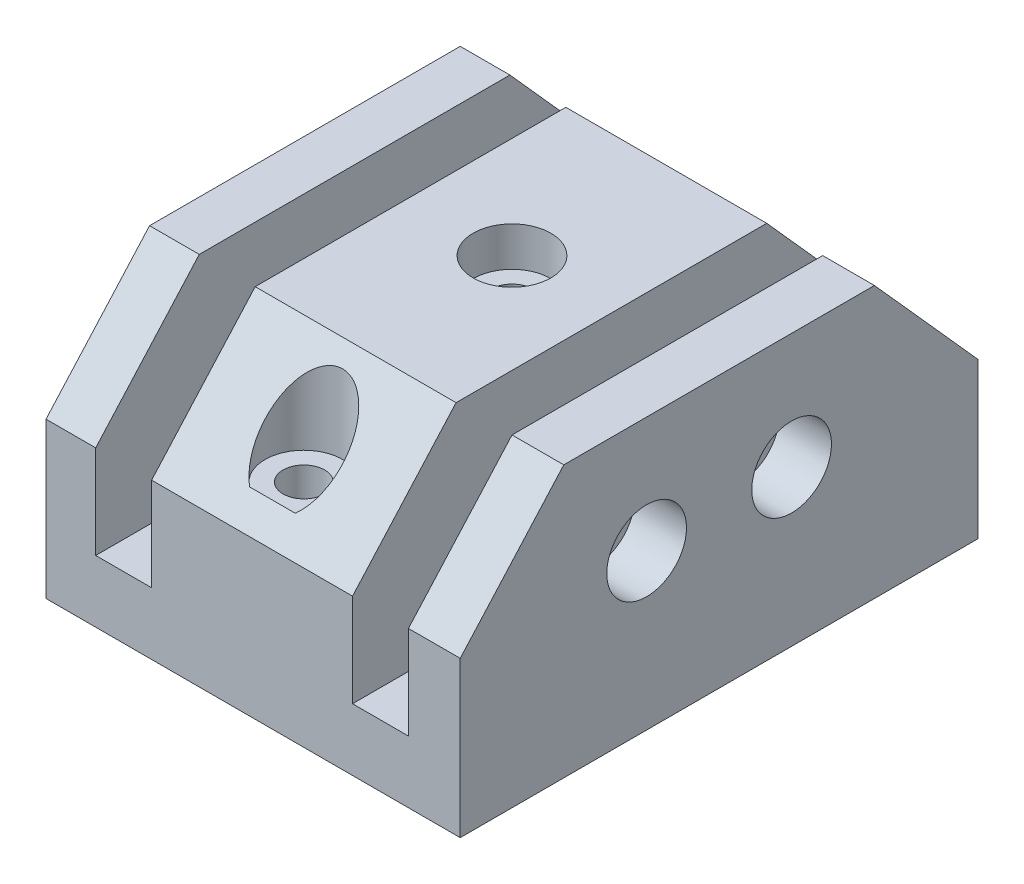
SolidWorks part; units mm, degrees
ref_plane "Front Plane" through (0, 0, 0) normal (0, 0, 1) x (1, 0, 0)
ref_plane "Top Plane" through (0, 0, 0) normal (0, 1, 0) x (1, 0, 0)
ref_plane "Right Plane" through (0, 0, 0) normal (1, 0, 0) x (0, 0, -1)
sketch "Sketch1" plane through (0, 0, 0) normal (1, 0, 0) x (0, 0, -1)
  line L1 (0, 0) -> (63.5, 0)
  line L2 (0, 0) -> (0, 6.35)
  line L3 (0, 6.35) -> (63.5, 6.35)
  line L4 (63.5, 0) -> (63.5, 6.35)
  dimension "D1" = 6.35
  dimension "D2" = 63.5
extrude "Boss-Extrude1" add sketch "Sketch1" against normal blind 50.8
sketch "Sketch2" plane through (0, 0, 0) normal (1, 0, 0) x (0, 0, -1)
  line L0 (0, 6.35) -> (0, 19.05)
  line L1 (0, 19.05) -> (12.7, 33.249)
  line L2 (12.7, 33.249) -> (50.8, 33.249)
  line L3 (50.8, 33.249) -> (63.5, 19.05)
  line L4 (63.5, 19.05) -> (63.5, 6.35)
  line L5 (63.5, 6.35) -> (0, 6.35)
  point P7 (31.75, 33.249)
  point P10 (31.75, 6.35)
  dimension "D1" = 38.1
  dimension "D2" = 12.7
  dimension "D3" = 12.7
  dimension "D4" = 19.05
  dimension "D5" = 19.05
extrude "Boss-Extrude2" add sketch "Sketch2" against normal blind 50.8
sketch "Sketch10" plane through (0, 0, -63.5) normal (0, 0, -1) x (-1, 0, 0)
  line L1 (50.8, 33.249) -> (0, 33.249) construction
  line L3 (6.35, 7.62) -> (6.35, 33.249)
  line L4 (6.35, 33.249) -> (13.208, 33.249)
  line L5 (13.208, 7.62) -> (13.208, 33.249)
  line L6 (6.35, 7.62) -> (13.208, 7.62)
  line L8 (50.8, 0) -> (0, 0) construction
  point P11 (13.208, 7.62)
  dimension "D1" = 7.62
  dimension "D2" = 6.858
  dimension "D3" = 6.35
extrude "Cut-Extrude1" cut sketch "Sketch10" against normal through all
pattern_linear "LPattern3" count 2 spacing 31.496 along (-1, 0, 0) of "Cut-Extrude1"
sketch "Sketch11" plane through (0, 0, 0) normal (1, 0, 0) x (0, 0, -1)
  circle A0 centre (22.86, 19.05) radius 4.8895
  circle A1 centre (22.86, 19.05) radius 7.9375 construction
  circle A2 centre (40.64, 19.05) radius 4.8895
  circle A3 centre (40.64, 19.05) radius 7.9375 construction
  dimension "D1" = 9.779
  dimension "D3" = 15.875
  dimension "D4" = 9.779
  dimension "D6" = 15.875
  dimension "D2" = 10.16
  dimension "D5" = 10.16
extrude "Cut-Extrude2" cut sketch "Sketch11" against normal through all
sketch "Sketch14" plane through (0, 33.249, 0) normal (0, 1, 0) x (1, 0, 0)
  line L3 (-37.846, 12.7) -> (-37.846, 50.8) construction
  point P0 (-25.4, 31.75)
  point P4 (-37.846, 31.75)
  dimension "D1" = 12.446
hole_wizard "CBORE for #10 Socket Head Cap Screw1" positions "Sketch15" profile "Sketch16" counterbore size "#10" standard "ANSI Inch" end condition up to next
sketch "Sketch15" plane through (0, 33.249, 0) normal (0, 1, 0) x (1, 0, 0)
  point P0 (-25.4, 31.75)
sketch "Sketch16" plane through (-25.4, 33.249, -31.75) normal (1, 0, 0) x (0, 0, 1)
  line L0 (0, 0) -> (0, 33.249)
  line L1 (0, 33.249) -> (2.5527, 33.249)
  line L3 (2.5527, 33.249) -> (2.5527, 4.826)
  line L4 (2.5527, 4.826) -> (4.7625, 4.826)
  line L5 (4.7625, 4.826) -> (4.7625, 0)
  line L7 (4.7625, 0) -> (0, 0)
  line L11 (0, -6.35) -> (0, 107.95) construction
  dimension "Thru Hole Dia." = 5.1054
  dimension "Thru Hole Depth" = 33.249
  dimension "C'Bore Dia." = 9.525
  dimension "C'Bore Depth" = 4.826
sketch "Sketch17" plane through (0, 40.0201, -44.7438) normal (0, 0.6667, -0.7454) x (-1, 0, 0)
  line L0 (13.208, -28.1343) -> (13.208, -9.0843) construction
  line L1 (37.846, -9.0843) -> (13.208, -9.0843) construction
  point P0 (25.527, -18.6093)
  point P4 (13.208, -18.6093)
  point P7 (25.527, -9.0843)
sketch "Sketch18" plane through (0, 8.4667, 9.466) normal (0, 0.6667, 0.7454) x (1, 0, 0)
  line L0 (-13.208, 33.249) -> (-13.208, 14.199) construction
  line L1 (-37.846, 33.249) -> (-13.208, 33.249) construction
  point P0 (-25.527, 23.724)
  point P1 (-25.527, 23.724)
  point P4 (-13.208, 23.724)
  point P7 (-25.527, 33.249)
ref_plane "Plane2" through (0, 33.02, 0) normal (0, -1, 0) x (-1, 0, 0)
hole_wizard "CBORE for #10 Socket Head Cap Screw3" positions "Sketch24" profile "Sketch25" counterbore size "#10" standard "ANSI Inch" end condition up to next
sketch "Sketch24" plane through (0, 33.02, 0) normal (0, -1, 0) x (-1, 0, 0)
  point P0 (25.527, 6.35)
  point P2 (25.527, 57.15)
sketch "Sketch25" plane through (-25.527, 33.02, -6.35) normal (1, 0, 0) x (0, 0, 1)
  line L0 (0, 0) -> (0, 33.02)
  line L1 (0, 33.02) -> (2.5527, 33.02)
  line L3 (2.5527, 33.02) -> (2.5527, 11.176)
  line L4 (2.5527, 11.176) -> (4.7625, 11.176)
  line L5 (4.7625, 11.176) -> (4.7625, 0)
  line L7 (4.7625, 0) -> (0, 0)
  line L11 (0, -6.35) -> (0, 107.95) construction
  dimension "Thru Hole Dia." = 5.1054
  dimension "Thru Hole Depth" = 33.02
  dimension "C'Bore Dia." = 9.525
  dimension "C'Bore Depth" = 11.176
ref_plane "midplane" through (0, 0, -31.75) normal (0, 0, -1) x (-1, 0, 0)
